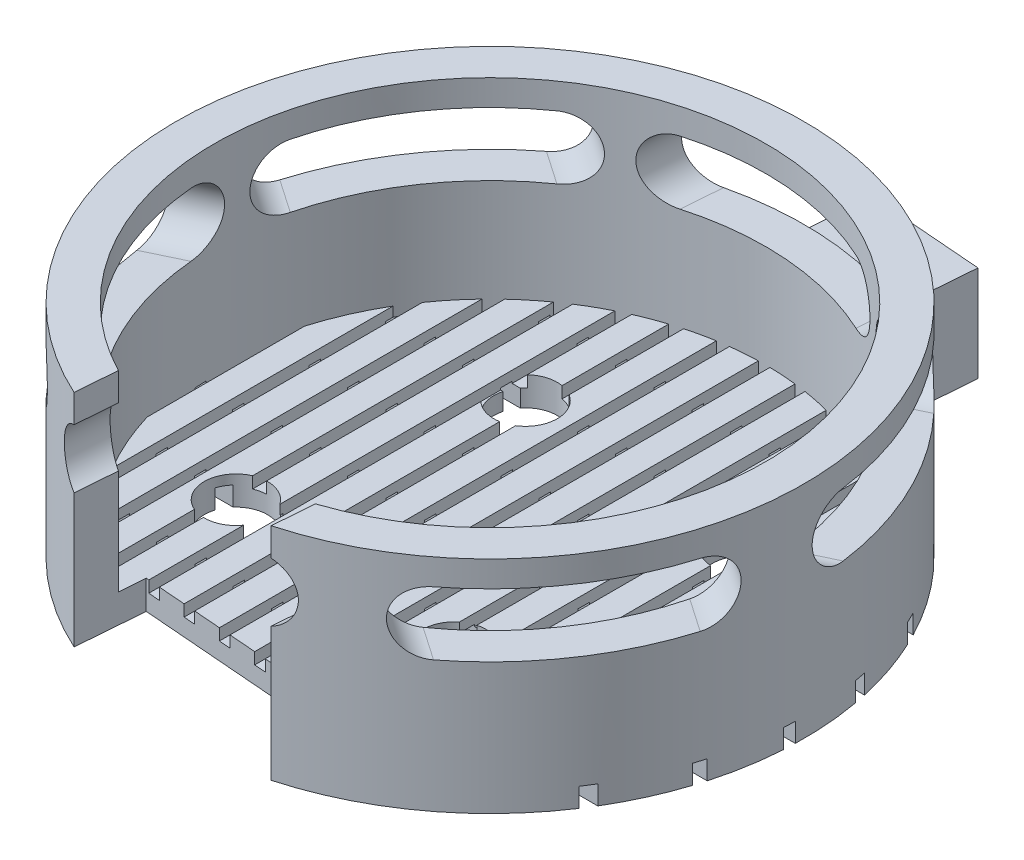
SolidWorks part; units mm, degrees
ref_plane "Plan de face" through (0, 0, 0) normal (0, 0, 1) x (1, 0, 0)
ref_plane "Plan de dessus" through (0, 0, 0) normal (0, 1, 0) x (1, 0, 0)
ref_plane "Plan de droite" through (0, 0, 0) normal (1, 0, 0) x (0, 0, -1)
sketch "Esquisse1" plane through (0, 0, 0) normal (0, 1, 0) x (1, 0, 0)
  circle A0 centre (0, 0) radius 14.375
  circle A1 centre (0, 0) radius 16.375
  dimension "D1" = 28.75
  dimension "D2" = 2
extrude "Boss.-Extru.1" add sketch "Esquisse1" along normal blind 10
sketch "Esquisse2" plane through (0, 0, 0) normal (0, -1, 0) x (1, 0, 0)
  circle A0 centre (0, 0) radius 16.375
  circle A1 centre (0, 0) radius 16.375 construction
extrude "Boss.-Extru.2" add sketch "Esquisse2" along normal blind 1.5
sketch "Esquisse3" plane through (0, -1.5, 0) normal (0, -1, 0) x (1, 0, 0)
  line L0 (0, 0) -> (-7.7269, 5.5267) construction
  line L1 (0, 0) -> (7.7269, -5.5267) construction
  line L2 (0, 0) -> (4.6541, 6.5069) construction
  line L3 (0, 0) -> (-4.6541, -6.5069) construction
  circle A0 centre (-7.7269, 5.5267) radius 1.65
  circle A1 centre (4.6541, 6.5069) radius 1.65
  circle A2 centre (-4.6541, -6.5069) radius 1.65
  circle A3 centre (7.7269, -5.5267) radius 1.65
  dimension "D1" = 3.3
  dimension "D2" = 19
  dimension "D3" = 16
extrude "Enlèv. mat.-Extru.1" cut sketch "Esquisse3" against normal blind 1.5
sketch "Esquisse4" plane through (0, -1.5, 0) normal (0, -1, 0) x (1, 0, 0)
  line L0 (4.6541, 6.5069) -> (-7.7269, 5.5267) construction
  line L1 (0, 0) -> (-1.6391, 20.7041) construction
  line L2 (-1.2924, 16.3239) -> (8.3904, 17.0905) construction
  line L3 (-6.5193, 11.4104) -> (4.6426, 12.2941)
  line L8 (-6.5193, 11.4104) -> (-7.2273, 20.3538)
  line L9 (-7.2273, 20.3538) -> (3.9346, 21.2375)
  line L10 (4.6426, 12.2941) -> (3.9346, 21.2375)
  line L11 (-6.5193, 11.4104) -> (3.9346, 21.2375) construction
  line L12 (-7.2273, 20.3538) -> (4.6426, 12.2941) construction
  circle A1 centre (0, 0) radius 16.375 construction
  point P6 (-1.2924, 16.3239)
  point P13 (-1.2924, 16.3239)
extrude "Enlèv. mat.-Extru.2" cut sketch "Esquisse4" against normal blind 16
sketch "Esquisse6" plane through (-0.9383, 0, 11.8522) normal (-0.0789, 0, 0.9969) x (0.9969, 0, 0.0789)
  line L0 (0, -1.5) -> (0, 10) construction
  line L1 (-5.5984, -1.5) -> (5.5984, -1.5) construction
  line L2 (14.375, 10) -> (-14.375, 10) construction
  line L3 (-5, 7) -> (5, 7) construction
  line L4 (-5, 8.65) -> (5, 8.65)
  line L5 (-5, 5.35) -> (5, 5.35)
  arc A0 (-5, 8.65) -> (-5, 5.35) centre (-5, 7) ccw
  arc A1 (5, 5.35) -> (5, 8.65) centre (5, 7) ccw
  point P8 (0, 7)
  dimension "D1" = 10
  dimension "D2" = 1.65
  dimension "D3" = 1.35
extrude "Enlèv. mat.-Extru.3" cut sketch "Esquisse6" against normal blind 35
pattern_circular "Répétition circulaire1" count 6 over 360 about axis through (0, -1.5, 0) along (0, -1, 0) of "Enlèv. mat.-Extru.3" other way count 2 other way every 60
sketch "Esquisse7" plane through (0, 0, 0) normal (0, 1, 0) x (1, 0, 0)
  line L0 (-12.375, -20.3427) -> (-11.775, -20.3427)
  line L5 (-14.375, -20.3427) -> (-13.775, -20.3427)
  line L6 (-14.375, -20.3427) -> (-14.375, 19.6573)
  line L7 (-14.375, 19.6573) -> (-13.775, 19.6573)
  line L8 (-13.775, -20.3427) -> (-13.775, 19.6573)
  line L9 (-11.775, -20.3427) -> (-11.775, 19.6573)
  line L10 (-12.375, 19.6573) -> (-11.775, 19.6573)
  line L11 (-12.375, -20.3427) -> (-12.375, 19.6573)
  line L12 (-10.375, -20.3427) -> (-9.775, -20.3427)
  line L13 (-9.775, -20.3427) -> (-9.775, 19.6573)
  line L14 (-10.375, 19.6573) -> (-9.775, 19.6573)
  line L15 (-10.375, -20.3427) -> (-10.375, 19.6573)
  line L16 (-8.375, -20.3427) -> (-7.775, -20.3427)
  line L17 (-7.775, -20.3427) -> (-7.775, 19.6573)
  line L18 (-8.375, 19.6573) -> (-7.775, 19.6573)
  line L19 (-8.375, -20.3427) -> (-8.375, 19.6573)
  line L20 (-6.375, -20.3427) -> (-5.775, -20.3427)
  line L21 (-5.775, -20.3427) -> (-5.775, 19.6573)
  line L22 (-6.375, 19.6573) -> (-5.775, 19.6573)
  line L23 (-6.375, -20.3427) -> (-6.375, 19.6573)
  line L24 (-4.375, -20.3427) -> (-3.775, -20.3427)
  line L25 (-3.775, -20.3427) -> (-3.775, 19.6573)
  line L26 (-4.375, 19.6573) -> (-3.775, 19.6573)
  line L27 (-4.375, -20.3427) -> (-4.375, 19.6573)
  line L28 (-2.375, -20.3427) -> (-1.775, -20.3427)
  line L29 (-1.775, -20.3427) -> (-1.775, 19.6573)
  line L30 (-2.375, 19.6573) -> (-1.775, 19.6573)
  line L31 (-2.375, -20.3427) -> (-2.375, 19.6573)
  line L32 (-0.375, -20.3427) -> (0.225, -20.3427)
  line L33 (0.225, -20.3427) -> (0.225, 19.6573)
  line L34 (-0.375, 19.6573) -> (0.225, 19.6573)
  line L35 (-0.375, -20.3427) -> (-0.375, 19.6573)
  line L36 (1.625, -20.3427) -> (2.225, -20.3427)
  line L37 (2.225, -20.3427) -> (2.225, 19.6573)
  line L38 (1.625, 19.6573) -> (2.225, 19.6573)
  line L39 (1.625, -20.3427) -> (1.625, 19.6573)
  line L40 (3.625, -20.3427) -> (4.225, -20.3427)
  line L41 (4.225, -20.3427) -> (4.225, 19.6573)
  line L42 (3.625, 19.6573) -> (4.225, 19.6573)
  line L43 (3.625, -20.3427) -> (3.625, 19.6573)
  line L44 (5.625, -20.3427) -> (6.225, -20.3427)
  line L45 (6.225, -20.3427) -> (6.225, 19.6573)
  line L46 (5.625, 19.6573) -> (6.225, 19.6573)
  line L47 (5.625, -20.3427) -> (5.625, 19.6573)
  line L48 (7.625, -20.3427) -> (8.225, -20.3427)
  line L49 (8.225, -20.3427) -> (8.225, 19.6573)
  line L50 (7.625, 19.6573) -> (8.225, 19.6573)
  line L51 (7.625, -20.3427) -> (7.625, 19.6573)
  line L52 (9.625, -20.3427) -> (10.225, -20.3427)
  line L53 (10.225, -20.3427) -> (10.225, 19.6573)
  line L54 (9.625, 19.6573) -> (10.225, 19.6573)
  line L55 (9.625, -20.3427) -> (9.625, 19.6573)
  line L56 (11.625, -20.3427) -> (12.225, -20.3427)
  line L57 (12.225, -20.3427) -> (12.225, 19.6573)
  line L58 (11.625, 19.6573) -> (12.225, 19.6573)
  line L59 (11.625, -20.3427) -> (11.625, 19.6573)
  line L60 (13.625, -20.3427) -> (14.225, -20.3427)
  line L61 (14.225, -20.3427) -> (14.225, 19.6573)
  line L62 (13.625, 19.6573) -> (14.225, 19.6573)
  line L63 (13.625, -20.3427) -> (13.625, 19.6573)
  arc A0 (4.536, -13.6406) -> (-6.6259, -12.7569) centre (0, 0) ccw construction
  circle A1 centre (0, 0) radius 14.375
  circle M62 centre (7.7269, 5.5267) radius 1.65
  circle M63 centre (-4.6541, 6.5069) radius 1.65
  circle M64 centre (-7.7269, -5.5267) radius 1.65
  circle M65 centre (4.6541, -6.5069) radius 1.65
  line M66 (-6.5193, -11.4104) -> (4.6426, -12.2941)
  arc M68 (4.536, -13.6406) -> (-6.6259, -12.7569) centre (0, 0) ccw
  dimension "D2" = 40
  dimension "D1" = 0.6
  dimension "D3" = 15
extrude "Enlèv. mat.-Extru.4" cut sketch "Esquisse7" against normal blind 0.6 contours L8 M68 | L11 L9 M68 | L15 L13 M68 | L19 L17 M64 M68 | L19 L17 M68 M64 | L23 L21 M66 M63 M68 M64 | L27 L25 M66 M63 | L27 L25 M63 M68 | L31 L29 M66 M68 | L35 L33 M66 M68 | L39 L37 M66 M68 | L43 L41 M65 M68 | L43 L41 M66 M65 | L47 L45 M68 M65 | L47 L45 M65 M62 M68 | L51 L49 M68 M62 | L51 L49 M62 M68 | L55 L53 M68 | L59 L57 M68 | L63 L61 M68 region at (-12.069, 0, 0) region at (-14.0154, 0, 0) region at (-10.0721, 0, 0) region at (-8.0721, 0, 9.5116) region at (-8.0741, 0, -3.984) region at (-6.0748, 0, -0.5938) region at (-4.0715, 0, -10.9123) region at (-4.0742, 0, 3.3153) region at (-2.0747, 0, -1.2306) region at (-0.0749, 0, -1.2266) region at (1.9249, 0, -1.0828) region at (3.9238, 0, -4.3939) region at (3.922, 0, 10.1049) region at (5.9234, 0, -3.7781) region at (5.9296, 0, 10.3034) region at (7.9217, 0, -9.5747) region at (7.924, 0, 4.0471) region at (9.9222, 0, 0) region at (11.9194, 0, 0) region at (13.8901, 0, 0)
sketch3d "Esquisse3D7" plane through (0, 0, 0) normal (0, 0, 1) x (1, 0, 0)
  dimension "D1" = 35
sketch "Esquisse8" plane through (1.824, 0, -23.0386) normal (-0.0789, 0, 0.9969) x (0.9969, 0, 0.0789)
  line L0 (0, 0) -> (0, 9.9971) construction
  line L1 (-16.375, -1.5) -> (16.375, -1.5) construction
  line L2 (-3, 3.5) -> (3, 3.5)
  line L3 (-3, 3.5) -> (-3, -1.5)
  line L4 (-3, -1.5) -> (3, -1.5)
  line L5 (3, 3.5) -> (3, -1.5)
  line L6 (-3, 3.5) -> (3, -1.5) construction
  line L7 (-3, -1.5) -> (3, 3.5) construction
  point P3 (0, 1)
  dimension "D1" = 5
  dimension "D2" = 6
extrude "Boss.-Extru.3" add sketch "Esquisse8" along normal up to surface (7.0128 mm away) up to face at (14.0335, 7.0825, -7.5948)
sketch "Esquisse9" plane through (2.9906, 0, 0.2368) normal (0.9969, 0, 0.0789) x (0.0789, 0, -0.9969)
  line L0 (16.0978, -1.5) -> (23.1107, -1.5) construction
  line L1 (23.1107, 3.5) -> (21.0978, 3.5)
  line L2 (23.1107, 3.5) -> (23.1107, -1.5)
  line L3 (23.1107, -1.5) -> (21.0978, -1.5)
  line L4 (21.0978, 3.5) -> (21.0978, -1.5)
  line L5 (16.0978, -1.5) -> (16.0978, 3.5) construction
  dimension "D1" = 5
extrude "Enlèv. mat.-Extru.5" cut sketch "Esquisse9" against normal blind 8.6
sketch "Esquisse11" plane through (0, -1.5, 0) normal (0, -1, 0) x (1, 0, 0)
  line L60 (0, -16.375) -> (0, 16.375) construction
  line L62 (20, -14.9034) -> (-20, -14.9034)
  line L63 (20, -14.9034) -> (20, -15.5034)
  line L64 (20, -15.5034) -> (-20, -15.5034)
  line L65 (-20, -14.9034) -> (-20, -15.5034)
  line L66 (20, -14.9034) -> (-20, -15.5034) construction
  line L67 (20, -15.5034) -> (-20, -14.9034) construction
  point P2 (0, -15.2034)
  dimension "D1" = 0.6
  dimension "D2" = 40
extrude "Enlèv. mat.-Extru.6" cut sketch "Esquisse11" against normal blind 1
pattern_linear "Répétition linéaire1" count 7 spacing 4 along (-0.0789, 0, 0.9969) of "Enlèv. mat.-Extru.6"
equation "\"entretoiseBearing\"= 1.5mm"
equation "\"length_tibia\"= 206mm"
equation "\"length_femur\"= 117mm"
equation "\"length_coxa\"= 27mm"
equation "\"height\"= 40mm"
equation "\"width\"= 100mm"
equation "\"lever\"= 40mm"
equation "\"errorFlat\"= 0.15mm"
equation "\"errorFlat_tight\"= 0.1mm"
equation "\"errorCircle\"= 0.30mm"
equation "\"errorCircle_tight\" = 0.15mm"
equation "\"cuticule\"=1.5mm"
equation "\"cuticule_attach_w\"=10mm"
equation "\"cuticule_attach_h\"=2.5mm"
equation "\"depthMagnet\"= 1mm"
equation "\"insert_d\" = 3.2mm"
equation "\"insert_l\" = 5mm"
equation "\"D1@Esquisse3\"= 3 + \"errorCircle\""
equation "\"D2@Esquisse6\"= 1.50mm + \"errorFlat\""
equation "\"D3@Esquisse6\"= 1.50mm -  \"errorFlat\""
